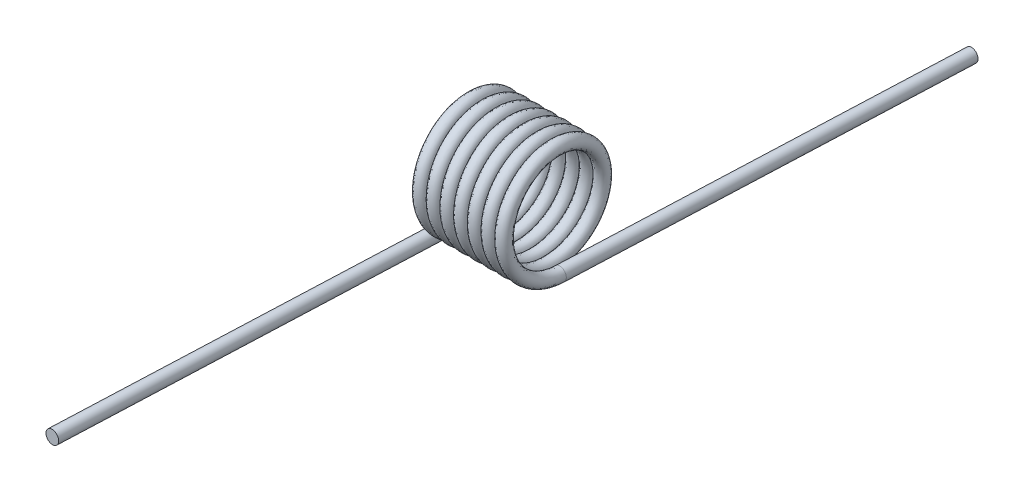
SolidWorks part; units mm, degrees
ref_plane "Front" through (0, 0, 0) normal (0, 0, 1) x (1, 0, 0)
ref_plane "Top" through (0, 0, 0) normal (0, 1, 0) x (1, 0, 0)
ref_plane "Right" through (0, 0, 0) normal (1, 0, 0) x (0, 0, -1)
sketch "Sketch1" plane through (0, 0, 0) normal (1, 0, 0) x (0, 0, -1)
  line L0 (0, -2.2098) -> (0, -2.8448) construction
  line L1 (0, -2.8448) -> (19.05, -2.8448) construction
  line L2 (0, -2.8448) -> (-19.05, -2.8448) construction
  line L3 (0, 0) -> (2.8448, 0) construction
  line L4 (0, 0) -> (0, -2.8448) construction
  line L5 (-19.05, -2.8448) -> (-19.05, -2.2098) construction
  line L6 (-19.05, -2.2098) -> (0, -2.2098) construction
  line L7 (19.05, -2.8448) -> (19.05, -2.2098) construction
  line L8 (19.05, -2.2098) -> (0, -2.2098) construction
  circle A0 centre (0, 0) radius 2.8448 construction
  circle A1 centre (0, 0) radius 1.778 construction
  circle A2 centre (0, 0) radius 2.5273 construction
  point P7 (0, -2.5273)
  point P10 (0, 2.8448)
  dimension "OD" = 5.6896
  dimension "For Shaft Diameter" = 3.556
  dimension "Wire Diameter" = 0.635
  dimension "Leg Length" = 19.05
  dimension "Deflection Angle" = 180
sketch "Sketch2" plane through (0, 0, 0) normal (1, 0, 0) x (0, 0, -1)
  circle A0 centre (0, 0) radius 2.5273 construction
  circle A2 centre (0, 0) radius 2.5273
curve "Helix/Spiral1" pitch 0.6604 height 4.6228 turns 7
ref_plane "Plane1" through (0, -2.5273, 0) normal (0.0416, 0, -0.9991) x (0.9989, -0.0232, 0.0415)
sketch "Sketch3" plane through (0, -2.5273, 0) normal (0.0416, 0, -0.9991) x (0.9989, -0.0232, 0.0415)
  circle A0 centre (0, 0) radius 0.3175
  dimension "D1" = 0.635
sweep "Sweep1" add profiles "Sketch3" path "Helix/Spiral1"
sketch "Sketch4" plane through (0, 0, 0) normal (-0.0416, 0, 0.9991) x (-0.9989, 0.0232, -0.0415)
  circle A1 centre (-0.0587, 2.5266) radius 0.3175
  circle A2 centre (-0.0587, 2.5266) radius 0.3175
  dimension "D1" = 0
extrude "Extrude1" add sketch "Sketch4" along normal blind 19.05
sketch "Sketch5" plane through (0.008, 0, -0.1919) normal (0.0416, 0, -0.9991) x (0.9933, -0.1083, 0.0413)
  circle A1 centre (4.8653, 2.0123) radius 0.3175
  circle A2 centre (4.8653, 2.0123) radius 0.3175
  dimension "D1" = 0
extrude "Extrude2" add sketch "Sketch5" along normal blind 19.05
sketch "Sketch6" plane through (0, 0, 0) normal (1, 0, 0) x (0, 0, -1)
  circle A2 centre (0, 0) radius 2.2098 construction
equation "\"D4@Helix/Spiral1\" = \"Wire Diameter@Sketch1\" + .001"
equation "\"D1@Sketch3\"=\"Wire Diameter@Sketch1\""
equation "\"D1@Extrude2\"=\"Leg Length@Sketch1\""
equation "\"Leg Length@Extrude1\"=\"Leg Length@Sketch1\""
